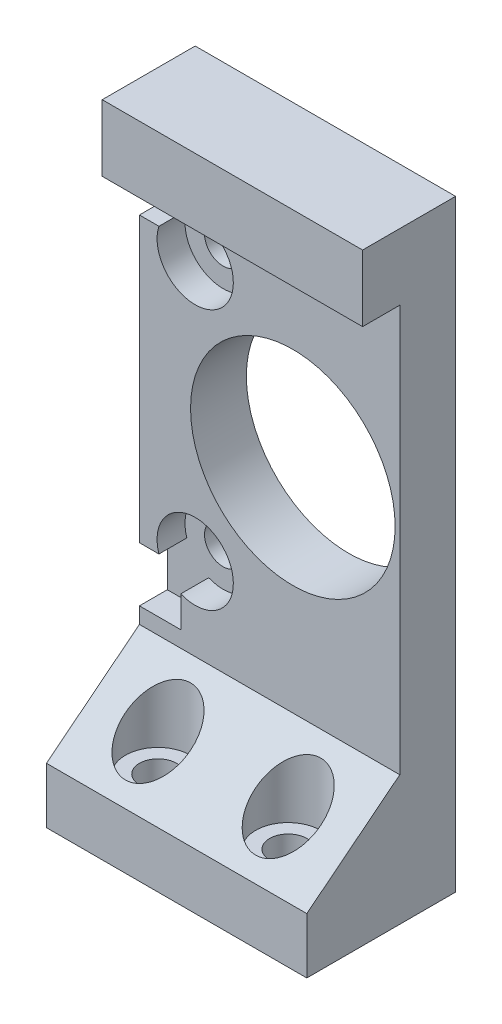
SolidWorks part; units mm, degrees
material "ABS"
ref_plane "Front Plane" through (0, 0, 0) normal (0, 0, 1) x (1, 0, 0)
ref_plane "Top Plane" through (0, 0, 0) normal (0, 1, 0) x (1, 0, 0)
ref_plane "Right Plane" through (0, 0, 0) normal (1, 0, 0) x (0, 0, -1)
sketch "Sketch1" plane through (0, 0, 0) normal (0, 0, 1) x (1, 0, 0)
  line L1 (-76.1871, 64.9281) -> (16.8129, 64.9281)
  line L2 (-76.1871, 64.9281) -> (-76.1871, -35.0719)
  line L3 (-76.1871, -35.0719) -> (16.8129, -35.0719)
  line L4 (16.8129, 64.9281) -> (16.8129, -35.0719)
  dimension "D1" = 93
  dimension "D2" = 100
extrude "Boss-Extrude2" add sketch "Sketch1" along normal blind 10 contours L1 L4 L3 L2
sketch "Sketch3" plane through (0, 0, 0) normal (0, 0, -1) x (-1, 0, 0)
  line L0 (76.1871, -35.0719) -> (-16.8129, -35.0719) construction
  line L1 (-16.8129, 64.9281) -> (-6.8129, 64.9281)
  line L2 (-16.8129, 64.9281) -> (-16.8129, -35.0719)
  line L3 (-16.8129, -35.0719) -> (-6.8129, -35.0719)
  line L4 (-6.8129, 64.9281) -> (-6.8129, -35.0719)
  line L5 (-16.8129, 64.9281) -> (-16.8129, -35.0719) construction
  dimension "D1" = 0
  dimension "D2" = 0
  dimension "D3" = 10
  dimension "D4" = 100
sketch "Sketch4" plane through (16.8129, 0, 0) normal (1, 0, 0) x (0, 0, -1)
  line L0 (-10, 64.9281) -> (-10, -35.0719) construction
  line L1 (-10, -5.0719) -> (0.01, -5.0719)
  line L2 (-10, -5.0719) -> (-10, -20.0719)
  line L3 (-10, -20.0719) -> (0.01, -20.0719)
  line L4 (0.01, -5.0719) -> (0.01, -20.0719)
  line L6 (-10, -35.0719) -> (0, -35.0719) construction
  dimension "D1" = 15
  dimension "D2" = 15
extrude "Boss-Extrude4" add sketch "Sketch4" along normal blind 24
sketch "Sketch5" plane through (0, -5.0719, 0) normal (0, 1, 0) x (1, 0, 0)
  line L0 (40.8129, -10) -> (16.8129, -10) construction
  line L2 (16.8129, 0) -> (16.8129, -10) construction
  circle A0 centre (26.8129, -5) radius 2
  dimension "D2" = 4
  dimension "D3" = 10
  dimension "D1" = 5
extrude "Cut-Extrude1" cut sketch "Sketch5" against normal blind 50
sketch "Sketch6" plane through (0, 0, 10) normal (0, 0, -1) x (-1, 0, 0)
  line L2 (76.1871, -35.0719) -> (-16.8129, -35.0719) construction
  line L3 (-16.8129, 64.9281) -> (-16.8129, -35.0719) construction
  circle A0 centre (-1.8129, -24.5719) radius 7.5
  dimension "D1" = 15
  dimension "D2" = 10.5
  dimension "D3" = 15
sketch "Sketch7" plane through (0, 0, 0) normal (0, 0, -1) x (-1, 0, 0)
  circle A0 centre (24.1871, 36.9281) radius 11
  circle A1 centre (24.1871, 36.9281) radius 9.3 construction
  dimension "D1" = 22
extrude "Cut-Extrude3" cut sketch "Sketch7" against normal blind 50
sketch "Sketch14" plane through (0, 0, 10) normal (0, 0, 1) x (1, 0, 0)
  line L0 (16.8129, 64.9281) -> (16.8129, -5.0719) construction
  line L1 (-44.6871, 15.7891) -> (16.8129, 15.7891)
  line L2 (-44.6871, 15.7891) -> (-44.6871, 57.7891)
  line L3 (-44.6871, 57.7891) -> (16.8129, 57.7891)
  line L4 (16.8129, 15.7891) -> (16.8129, 57.7891)
  dimension "D1" = 42
  dimension "D3" = 61.5
extrude "Cut-Extrude8" cut sketch "Sketch14" against normal blind 4
sketch "Sketch15" plane through (0, 0, 0) normal (0, 0, -1) x (-1, 0, 0)
  circle A0 centre (24.1871, 36.9281) radius 10
  circle A1 centre (24.1871, 36.9281) radius 11 construction
  dimension "D1" = 20
  dimension "D2" = 0
sketch "Sketch16" plane through (0, 0, 10) normal (0, 0, 1) x (1, 0, 0)
  line L0 (-43.6871, 56.9281) -> (14.3129, 56.9281) construction
  line L1 (-44.1871, 57.3281) -> (16.8129, 57.3281)
  line L2 (-44.1871, 57.3281) -> (-44.1871, 64.9281)
  line L3 (-44.1871, 64.9281) -> (16.8129, 64.9281)
  line L4 (16.8129, 57.3281) -> (16.8129, 64.9281)
  dimension "D1" = 0.4
sketch "Sketch17" plane through (0, 0, 10) normal (0, 0, 1) x (1, 0, 0)
  line L0 (16.8129, 15.7891) -> (16.8129, -5.0719) construction
  line L1 (-44.1871, 16.7281) -> (16.8129, 16.7281)
  line L2 (-44.1871, 16.7281) -> (-44.1871, -20.0719)
  line L3 (-44.1871, -20.0719) -> (16.8129, -20.0719)
  line L4 (16.8129, 16.7281) -> (16.8129, -20.0719)
  line L5 (-43.6871, 16.9281) -> (14.3129, 16.9281) construction
  line L6 (40.8129, -20.0719) -> (16.8129, -20.0719) construction
  line L9 (16.8129, -20.0719) -> (40.8129, -20.0719)
  line L10 (16.8129, -20.0719) -> (16.8129, -5.0719)
  line L11 (16.8129, -5.0719) -> (40.8129, -5.0719)
  line L12 (40.8129, -20.0719) -> (40.8129, -5.0719)
  line L13 (16.8129, -20.0719) -> (40.8129, -5.0719) construction
  line L14 (16.8129, -5.0719) -> (40.8129, -20.0719) construction
  point P16 (28.8129, -12.5719)
  dimension "D1" = 0.2
  dimension "D2" = 0
sketch "Sketch19" plane through (0, 0, 0) normal (0, 0, -1) x (-1, 0, 0)
  line L1 (-16.8129, 64.9281) -> (-16.8129, -35.0719) construction
  circle A0 centre (53.1871, 36.9281) radius 11
  circle A1 centre (24.1871, 36.9281) radius 10 construction
  dimension "D1" = 22
  dimension "D3" = 0
  dimension "D2" = 70
extrude "Cut-Extrude11" cut sketch "Sketch19" against normal blind 15
sketch "Sketch20" plane through (0, 0, 6) normal (0, 0, 1) x (1, 0, 0)
  circle A0 centre (-34.6871, 50.9281) radius 2
  circle A1 centre (5.3129, 50.9281) radius 2
  circle A2 centre (-34.6871, 22.9281) radius 2
  circle A3 centre (5.3129, 22.9281) radius 2
  arc A5 (-27.0471, 34.1316) -> (-27.0471, 39.7246) centre (-24.1871, 36.9281) ccw construction
  circle A6 centre (-24.1871, 36.9281) radius 11 construction
  dimension "D1" = 4
  dimension "D2" = 4
  dimension "D3" = 4
  dimension "D4" = 4
  dimension "D5" = 0
  dimension "D6" = 28
  dimension "D7" = 0
  dimension "D8" = 40
  dimension "D9" = 14
  dimension "D10" = 10.5
  dimension "D11" = 28
  dimension "D12" = 40
extrude "Cut-Extrude12" cut sketch "Sketch20" against normal blind 10
sketch "Sketch8" plane through (0, 64.9281, 0) normal (0, 1, 0) x (1, 0, 0)
  line L0 (-76.1871, -10) -> (16.8129, -10) construction
  line L5 (16.8129, 0) -> (12.3014, -10) construction
  line L6 (16.8129, -10) -> (7.8859, 0) construction
  line L8 (16.8129, -10) -> (16.8129, 0) construction
  line L9 (-76.1871, 0) -> (16.8129, 0) construction
  circle A0 centre (11.8129, -7) radius 1.4
  circle A1 centre (-13.1871, -7) radius 1.4
  point P4 (13.816, -6.6429)
  dimension "D1" = 25
  dimension "D2" = 5
  dimension "D3" = 2.8
  dimension "D4" = 7
  dimension "D5" = 7
sketch "Sketch21" plane through (0, 0, 0) normal (0, 0, -1) x (-1, 0, 0)
  line L1 (76.1871, 64.9281) -> (36.1871, 64.9281)
  line L2 (76.1871, 64.9281) -> (76.1871, 58.9281)
  line L3 (76.1871, 58.9281) -> (36.1871, 58.9281)
  line L4 (36.1871, 64.9281) -> (36.1871, 58.9281)
  dimension "D1" = 6
  dimension "D2" = 40
extrude "Boss-Extrude5" add sketch "Sketch21" along normal blind 27
sketch "Sketch22" plane through (0, 58.9281, 0) normal (0, -1, 0) x (1, 0, 0)
  line L0 (-76.1871, -27) -> (-76.1871, 0) construction
  line L1 (-36.1871, -27) -> (-76.1871, -27)
  line L2 (-36.1871, -27) -> (-36.1871, -20.7)
  line L3 (-36.1871, -20.7) -> (-76.1871, -20.7)
  line L4 (-76.1871, -27) -> (-76.1871, -20.7)
  dimension "D1" = 6.3
extrude "Boss-Extrude7" add sketch "Sketch22" along normal blind 40
sketch "Sketch23" plane through (0, 0, 10) normal (0, 0, 1) x (1, 0, 0)
  circle A0 centre (-53.1871, 36.9281) radius 8
  arc A1 (-44.6871, 43.9102) -> (-44.6871, 29.9459) centre (-53.1871, 36.9281) ccw construction
  dimension "D1" = 16
  dimension "D2" = 0
extrude "Cut-Extrude13" cut sketch "Sketch23" against normal blind 40
sketch "Sketch24" plane through (0, 0, 10) normal (0, 0, 1) x (1, 0, 0)
  line L1 (-76.1871, -35.0719) -> (42.0908, -35.0719)
  line L2 (-76.1871, -35.0719) -> (-76.1871, 6.7281)
  line L3 (-76.1871, 6.7281) -> (42.0908, 6.7281)
  line L4 (42.0908, -35.0719) -> (42.0908, 6.7281)
  dimension "D1" = 41.8
extrude "Cut-Extrude14" cut sketch "Sketch24" against normal blind 40
sketch "Sketch25" plane through (0, 0, 10) normal (0, 0, 1) x (1, 0, 0)
  line L5 (-44.6871, 29.9459) -> (-44.6871, 15.7891) construction
  line L6 (-76.1871, 6.7281) -> (-44.6871, 6.7281)
  line L7 (-76.1871, 6.7281) -> (-76.1871, 29.9281)
  line L8 (-76.1871, 29.9281) -> (-44.6871, 29.9281)
  line L9 (-44.6871, 6.7281) -> (-44.6871, 29.9281)
  arc A2 (-44.6871, 43.9102) -> (-44.6871, 29.9459) centre (-53.1871, 36.9281) ccw construction
  dimension "D1" = 7
extrude "Cut-Extrude15" cut sketch "Sketch25" against normal blind 20
sketch "Sketch26" plane through (0, 0, 6) normal (0, 0, 1) x (1, 0, 0)
  line L1 (-44.6871, 15.7891) -> (-36.2375, 15.7891)
  line L2 (-44.6871, 15.7891) -> (-44.6871, 21.6647)
  line L3 (-44.6871, 21.6647) -> (-36.2375, 21.6647)
  line L4 (-36.2375, 15.7891) -> (-36.2375, 21.6647)
  line L5 (-44.6871, 57.7891) -> (-36.2375, 57.7891)
  line L6 (-44.6871, 57.7891) -> (-44.6871, 52.1914)
  line L7 (-44.6871, 52.1914) -> (-36.2375, 52.1914)
  line L8 (-36.2375, 57.7891) -> (-36.2375, 52.1914)
  line L9 (6.8634, 52.1914) -> (14.3021, 52.1914)
  line L10 (6.8634, 52.1914) -> (6.8634, 57.7891)
  line L11 (6.8634, 57.7891) -> (14.3021, 57.7891)
  line L12 (14.3021, 52.1914) -> (14.3021, 57.7891)
  line L13 (6.8634, 20.9281) -> (14.3021, 20.9281)
  line L14 (6.8634, 20.9281) -> (6.8634, 15.7891)
  line L15 (6.8634, 15.7891) -> (14.3021, 15.7891)
  line L16 (14.3021, 20.9281) -> (14.3021, 15.7891)
  circle A0 centre (-34.6871, 22.9281) radius 2 construction
  circle A1 centre (-34.6871, 50.9281) radius 2 construction
  circle A2 centre (5.3129, 50.9281) radius 2 construction
  circle A3 centre (5.3129, 22.9281) radius 4
  circle A4 centre (5.3129, 50.9281) radius 4
  circle A5 centre (-34.6871, 50.9281) radius 4
  circle A6 centre (-34.6871, 22.9281) radius 4
  circle A7 centre (5.3129, 50.9281) radius 4
  circle A8 centre (5.3129, 22.9281) radius 4
  circle A9 centre (-34.6871, 50.9281) radius 4
  circle A10 centre (-34.6871, 22.9281) radius 4
  line M5 (-44.6871, 57.7891) -> (-44.6871, 43.9102)
  line M8 (-44.6871, 29.9281) -> (-44.6871, 15.7891)
  line M9 (-44.6871, 15.7891) -> (16.8129, 15.7891)
  line M11 (16.8129, 57.7891) -> (-44.6871, 57.7891)
  dimension "D1" = 8
  dimension "D2" = 8
  dimension "D3" = 8
  dimension "D4" = 8
extrude "Cut-Extrude18" cut sketch "Sketch26" against normal blind 3 contours A4 L9 L12 L10 M11 | A3 L14 L16 L13 M9 | A5 L8 L7 M11 M5 | A6 L3 L4 M8 M9 region at (-40.7189, 18.5733, 6) region at (10.7466, 18.2528, 6) region at (10.8466, 55.1634, 6) region at (-40.7326, 55.141, 6)
sketch "Sketch27" plane through (0, 0, 6) normal (0, 0, 1) x (1, 0, 0)
  circle A0 centre (5.3129, 50.9281) radius 4.1
  circle A1 centre (5.3129, 22.9281) radius 4
  circle A2 centre (-34.6871, 50.9281) radius 4.1
  circle A3 centre (-34.6871, 22.9281) radius 4.1
  dimension "D1" = 8.2
  dimension "D2" = 8.2
  dimension "D3" = 8
  dimension "D4" = 8.2
extrude "Cut-Extrude29" cut sketch "Sketch27" against normal blind 3
sketch "Sketch28" plane through (0, 0, 0) normal (0, 0, -1) x (-1, 0, 0)
  line L5 (-16.8129, 6.7281) -> (44.6871, 6.7281) construction
  line L6 (-16.8129, 64.9281) -> (12.6871, 64.9281)
  line L7 (-16.8129, 64.9281) -> (-16.8129, 6.7281)
  line L8 (-16.8129, 6.7281) -> (12.6871, 6.7281)
  line L9 (12.6871, 64.9281) -> (12.6871, 6.7281)
  circle A1 centre (34.6871, 22.9281) radius 2 construction
  dimension "D1" = 22
extrude "Cut-Extrude30" cut sketch "Sketch28" against normal blind 23
sketch "Sketch29" plane through (0, 15.7891, 0) normal (0, 1, 0) x (1, 0, 0)
  line L1 (-44.6871, -10) -> (-12.6871, -10)
  line L2 (-44.6871, -10) -> (-44.6871, -6)
  line L3 (-44.6871, -6) -> (-12.6871, -6)
  line L4 (-12.6871, -10) -> (-12.6871, -6)
extrude "Cut-Extrude31" cut sketch "Sketch29" against normal blind 23
sketch "Sketch31" plane through (0, 6.7281, 0) normal (0, -1, 0) x (1, 0, 0)
  line L1 (-44.6871, 6) -> (-12.6871, 6)
  line L2 (-44.6871, 6) -> (-44.6871, 0)
  line L3 (-44.6871, 0) -> (-12.6871, 0)
  line L4 (-12.6871, 6) -> (-12.6871, 0)
extrude "Boss-Extrude9" add sketch "Sketch31" along normal blind 6.6
sketch "Sketch32" plane through (0, 0, 6) normal (0, 0, 1) x (1, 0, 0)
  line L0 (-12.6871, 0.1281) -> (-12.6871, 57.7891) construction
  line L1 (-44.6871, 0.1281) -> (-12.6871, 0.1281)
  line L2 (-44.6871, 0.1281) -> (-44.6871, 6.1281)
  line L3 (-44.6871, 6.1281) -> (-12.6871, 6.1281)
  line L4 (-12.6871, 0.1281) -> (-12.6871, 6.1281)
  dimension "D1" = 6
extrude "Boss-Extrude10" add sketch "Sketch32" along normal blind 10
sketch "Sketch33" plane through (0, 6.1281, 0) normal (0, 1, 0) x (1, 0, 0)
  line L0 (-12.6871, -16) -> (-44.6871, -16) construction
  line L1 (-44.6871, -16) -> (-44.6871, -6) construction
  line L2 (-12.6871, -16) -> (-12.6871, -6) construction
  circle A0 centre (-33.6871, -11) radius 2
  circle A1 centre (-19.6871, -11) radius 2
  point P8 (-44.6871, -11)
  dimension "D1" = 4
  dimension "D2" = 4
  dimension "D3" = 0
  dimension "D4" = 5
  dimension "D5" = 11
  dimension "D6" = 7
extrude "Cut-Extrude32" cut sketch "Sketch33" against normal blind 10
sketch "Sketch34" plane through (-12.6871, 0, 0) normal (1, 0, 0) x (0, 0, -1)
  line L0 (-16, 6.1281) -> (-6, 6.1281)
  line L1 (-6, 6.1281) -> (-6, 14.0584)
  line L2 (-6, 6.1281) -> (-6, 57.7891) construction
  line L3 (-6, 14.0584) -> (-16, 6.1281)
extrude "Boss-Extrude11" add sketch "Sketch34" against normal up to vertex (32 mm away) up to point (-44.6871, 29.9281, 6)
sketch "Sketch35" plane through (0, 6.1281, 0) normal (0, -1, 0) x (1, 0, 0)
  circle A0 centre (-19.6871, 11) radius 3.5
  circle A1 centre (-33.6871, 11) radius 3.5
  dimension "D1" = 7
  dimension "D2" = 7
extrude "Cut-Extrude33" cut sketch "Sketch35" against normal blind 10
sketch "Sketch36" plane through (-36.1871, 0, 0) normal (1, 0, 0) x (0, 0, -1)
  line L1 (0, 64.9281) -> (27, 64.9281)
  line L2 (0, 64.9281) -> (0, 18.9281)
  line L3 (0, 18.9281) -> (27, 18.9281)
  line L4 (27, 64.9281) -> (27, 18.9281)
extrude "Cut-Extrude34" cut sketch "Sketch36" against normal blind 50
sketch "Sketch38" plane through (0, 0, 10) normal (0, 0, 1) x (1, 0, 0)
  line L0 (-76.1871, 64.9281) -> (-12.6871, 64.9281) construction
  line L1 (-76.1871, 29.9281) -> (-44.4371, 29.9281)
  line L2 (-76.1871, 29.9281) -> (-76.1871, 64.9281)
  line L3 (-76.1871, 64.9281) -> (-44.4371, 64.9281)
  line L4 (-44.4371, 29.9281) -> (-44.4371, 64.9281)
extrude "Cut-Extrude35" cut sketch "Sketch38" against normal blind 50
sketch "Sketch40" plane through (0, 0, 16) normal (0, 0, 1) x (1, 0, 0)
  line L1 (-44.6871, 0.1281) -> (-40.6871, 0.1281)
  line L2 (-44.6871, 0.1281) -> (-44.6871, 77.9464)
  line L3 (-44.6871, 77.9464) -> (-40.6871, 77.9464)
  line L4 (-40.6871, 0.1281) -> (-40.6871, 77.9464)
  dimension "D1" = 4
extrude "Cut-Extrude37" cut sketch "Sketch40" against normal blind 110
